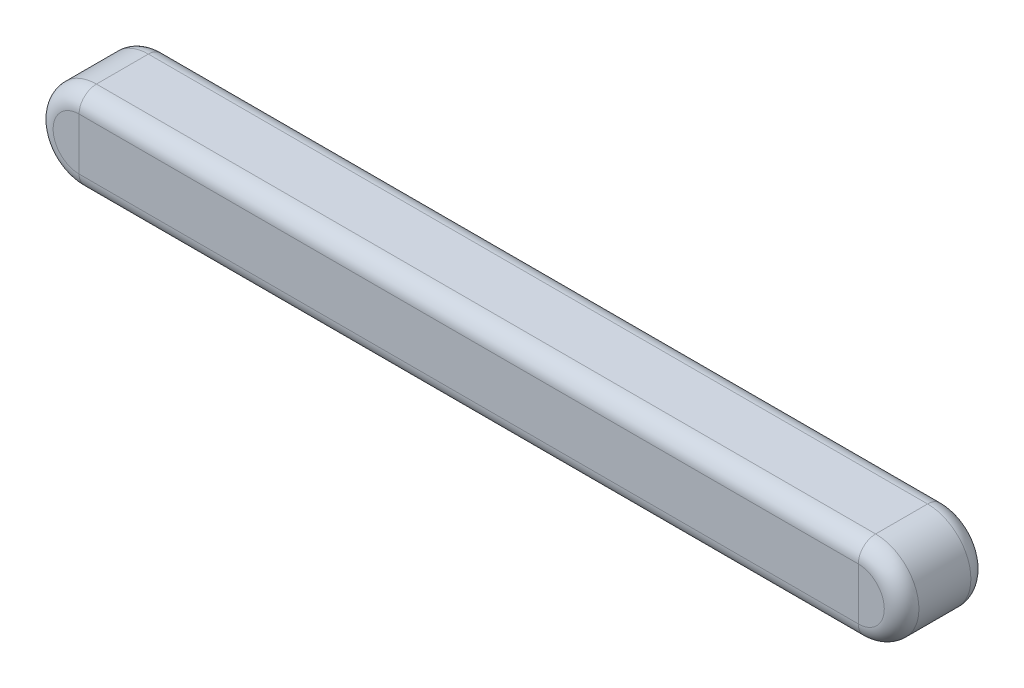
SolidWorks part; units mm, degrees
ref_plane "Front Plane" through (0, 0, 0) normal (0, 0, 1) x (1, 0, 0)
ref_plane "Top Plane" through (0, 0, 0) normal (0, 1, 0) x (1, 0, 0)
ref_plane "Right Plane" through (0, 0, 0) normal (1, 0, 0) x (0, 0, -1)
sketch "Sketch1" plane through (0, 0, 0) normal (0, 0, 1) x (1, 0, 0)
  line L1 (0, 0) -> (114.3, 0)
  line L3 (0, -12.7) -> (114.3, -12.7)
  arc A0 (114.3, 0) -> (114.3, -12.7) centre (114.3, -6.35) cw
  arc A1 (0, 0) -> (0, -12.7) centre (0, -6.35) ccw
  dimension "D1" = 114.3
  dimension "D4" = 12.7
extrude "Boss-Extrude1" add sketch "Sketch1" against normal blind 12.7
sketch "Sketch2" plane through (0, 0, -12.7) normal (0, 0, -1) x (-1, 0, 0)
  line L1 (-57.15, 0) -> (-57.15, -12.7) construction
  line L2 (-114.3, 0) -> (0, 0) construction
  line L3 (0, -12.7) -> (-114.3, -12.7) construction
  arc A1 (-114.3, 0) -> (-114.3, -12.7) centre (-114.3, -6.35) ccw construction
  circle A3 centre (-6.985, -6.35) radius 4.7625
  circle A5 centre (-107.315, -6.35) radius 4.7625
  point P7 (-120.65, -6.35)
  dimension "D1" = 50.165
  dimension "D2" = 9.525
extrude "Cut-Extrude1" cut sketch "Sketch2" against normal blind 6.35 contours A5 | A3 region at (6.985, -6.35, -12.7) region at (107.315, -6.35, -12.7)
ref_plane "Plane1" through (57.15, 0, 0) normal (1, 0, 0) x (0, 0, -1)
sketch "Sketch3" plane through (0, 0, 0) normal (0, 0, 1) x (1, 0, 0)
  line L0 (0, 0) -> (0, -12.7)
  line L1 (114.3, 0) -> (114.3, -12.7)
  line L2 (114.3, -12.7) -> (0, -12.7)
  line L3 (0, 0) -> (114.3, 0)
sketch "Sketch4" plane through (0, 0, -12.7) normal (0, 0, -1) x (-1, 0, 0)
  line L0 (0, -12.7) -> (0, 0)
  line L1 (-114.3, -12.7) -> (-114.3, 0)
  line L2 (-114.3, 0) -> (0, 0)
  line L3 (0, -12.7) -> (-114.3, -12.7)
split line "Split Line1"
split line "Split Line2"
fillet "Fillet1" radius 2.54 8 edges at (120.65, -6.35, 0) (-6.35, -6.35, 0) (120.65, -6.35, -12.7) (-6.35, -6.35, -12.7) (57.15, -12.7, -12.7) (57.15, -12.7, 0) (57.15, 0, 0) (57.15, 0, -12.7)
